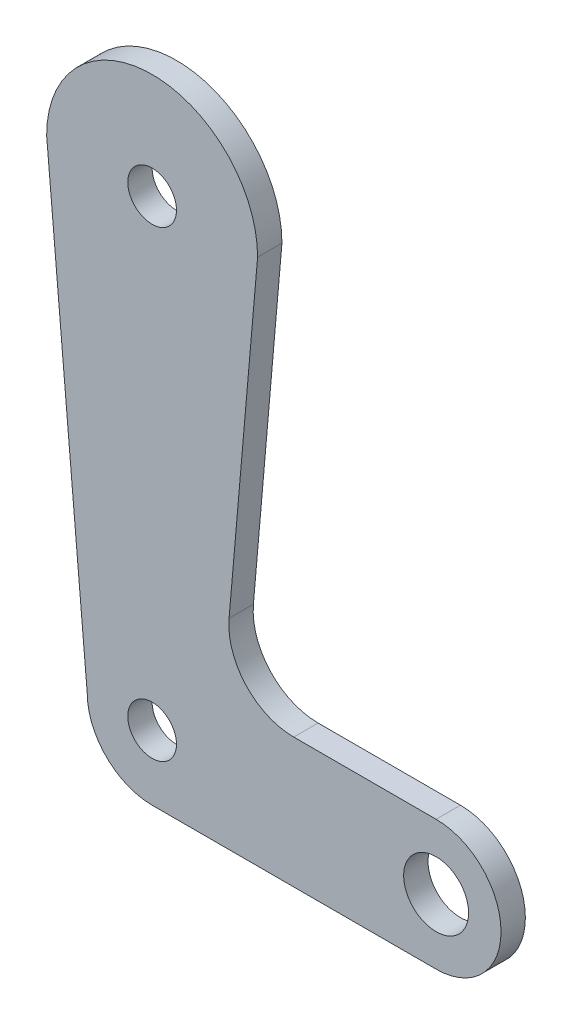
SolidWorks part; units mm, degrees
ref_plane "Piano frontale" through (0, 0, 0) normal (0, 0, 1) x (1, 0, 0)
ref_plane "Piano superiore" through (0, 0, 0) normal (0, 1, 0) x (1, 0, 0)
ref_plane "Piano destro" through (0, 0, 0) normal (1, 0, 0) x (0, 0, -1)
sketch "Schizzo1" plane through (0, 0, 0) normal (0, 0, 1) x (1, 0, 0)
  line L0 (35, 0) -> (0, 0) construction
  line L1 (35, -8) -> (0, -8)
  line L2 (35, 8) -> (17.4528, 8)
  line L3 (0, 0) -> (0, 57) construction
  line L4 (0, 57) -> (-38.8044, 57) construction
  line L5 (0, 0) -> (-38.8044, 0) construction
  line L6 (-13, 57) -> (-8, 0)
  line L7 (13, 57) -> (9.4831, 16.6954)
  arc A0 (35, -8) -> (35, 8) centre (35, 0) ccw
  arc A1 (-8, 0) -> (0, -8) centre (0, 0) ccw
  circle A2 centre (35, 0) radius 4
  circle A3 centre (0, 0) radius 3
  arc A4 (13, 57) -> (-13, 57) centre (0, 57) ccw
  circle A5 centre (0, 57) radius 3
  arc A6 (9.4831, 16.6954) -> (17.4528, 8) centre (17.4528, 16) ccw
  point P2 (0, 0)
  dimension "D3" = 8
  dimension "D4" = 6
  dimension "D5" = 26
  dimension "D7" = 6
  dimension "D8" = 8
  dimension "D9" = 8
  dimension "D11" = 16
  dimension "D12" = 38.8044
  dimension "D1" = 35
  dimension "D2" = 16
  dimension "D6" = 57
  dimension "D10" = 10
base flange "Base-Flangia3" sketch "Schizzo1" thickness 3 reverse thickness direction no parameters "D1"=0.7366
sketch "Linee di piegatura9" [suppressed] plane through (0, 0, 0) normal (0, 1, 0) x (1, 0, 0)
sketch "Casella di contorno9" [suppressed] plane through (0, 0, 0) normal (0, 1, 0) x (1, 0, 0)
sheet metal parameters "Lamiera8" thickness 3 parameters "D1"=0.7366
flat pattern "Ripetizione piatta8" [suppressed]
sketch "Linee di piegatura10" plane through (0, 0, 0) normal (0, 1, 0) x (1, 0, 0)
sketch3d "Casella di contorno10" [suppressed]
  line L0 (-1.6494, 73.242, 0) -> (-8.664, -7.2755, 0) construction
  line L1 (49.0303, 68.8268, 0) -> (42.0157, -11.6907, 0) construction
  line L2 (-1.6494, 73.242, 0) -> (49.0303, 68.8268, 0) construction
  line L3 (-8.664, -7.2755, 0) -> (42.0157, -11.6907, 0) construction
